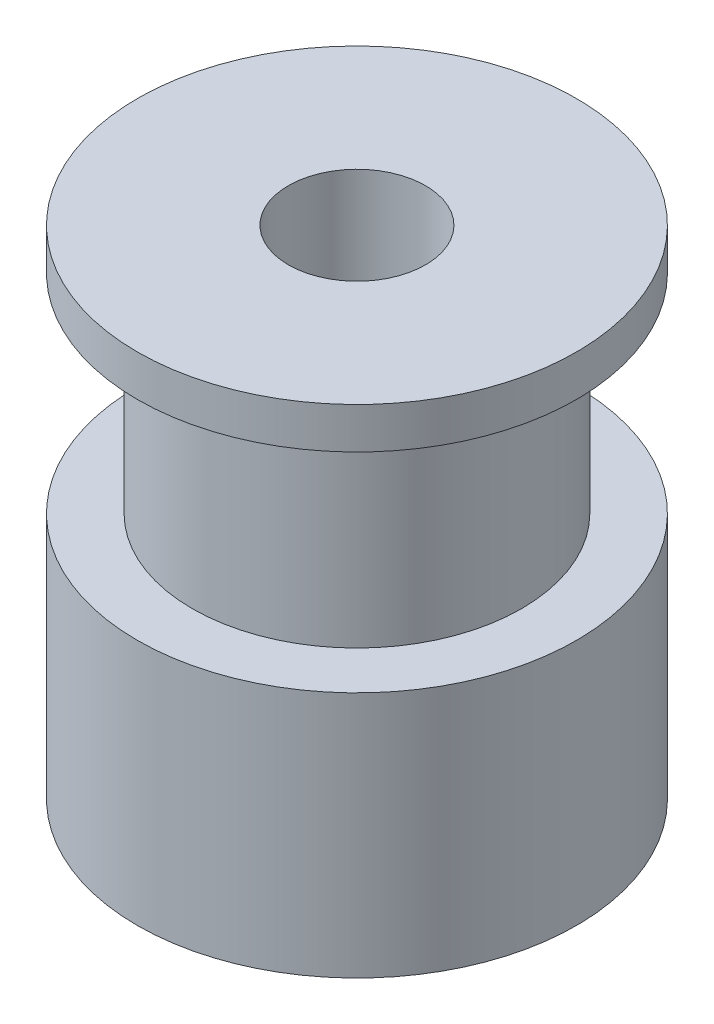
SolidWorks part; units mm, degrees
material "6061 Alloy"
ref_plane "Front Plane" through (0, 0, 0) normal (0, 0, 1) x (1, 0, 0)
ref_plane "Top Plane" through (0, 0, 0) normal (0, 1, 0) x (1, 0, 0)
ref_plane "Right Plane" through (0, 0, 0) normal (1, 0, 0) x (0, 0, -1)
sketch "Sketch1" plane through (0, 0, 0) normal (0, 1, 0) x (1, 0, 0)
  circle A0 centre (0, 0) radius 8
  dimension "D1" = 16
extrude "Boss-Extrude1" add sketch "Sketch1" along normal blind 9
sketch "Sketch2" plane through (0, 9, 0) normal (0, 1, 0) x (1, 0, 0)
  circle A0 centre (0, 0) radius 6
  dimension "D1" = 12
extrude "Boss-Extrude2" add sketch "Sketch2" along normal blind 7.6
sketch "Sketch3" plane through (0, 16.6, 0) normal (0, 1, 0) x (1, 0, 0)
  circle A0 centre (0, 0) radius 8
  dimension "D1" = 16
extrude "Boss-Extrude3" add sketch "Sketch3" along normal blind 1.5
sketch "Sketch4" plane through (0, 18.1, 0) normal (0, 1, 0) x (1, 0, 0)
  circle A0 centre (0, 0) radius 2.5
  dimension "D1" = 5
extrude "Cut-Extrude1" cut sketch "Sketch4" against normal through all
